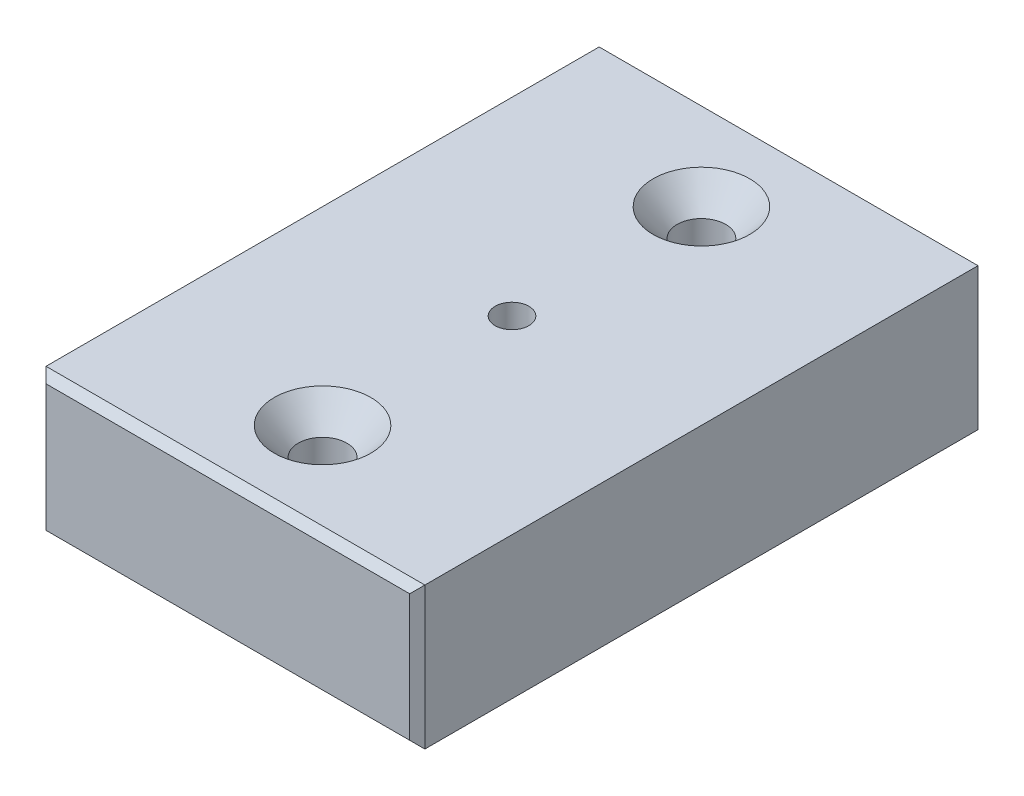
SolidWorks part; units mm, degrees
material "6061 Alloy"
ref_plane "Front Plane" through (0, 0, 0) normal (0, 0, 1) x (1, 0, 0)
ref_plane "Top Plane" through (0, 0, 0) normal (0, 1, 0) x (1, 0, 0)
ref_plane "Right Plane" through (0, 0, 0) normal (1, 0, 0) x (0, 0, -1)
sketch "Sketch1" plane through (0, 0, 0) normal (0, 0, 1) x (1, 0, 0)
  line L1 (12.7, -4.7625) -> (-12.7, -4.7625)
  line L2 (12.7, -4.7625) -> (12.7, 4.7625)
  line L3 (12.7, 4.7625) -> (-12.7, 4.7625)
  line L4 (-12.7, -4.7625) -> (-12.7, 4.7625)
  line L5 (12.7, -4.7625) -> (-12.7, 4.7625) construction
  line L6 (12.7, 4.7625) -> (-12.7, -4.7625) construction
  point P0 (0, 0)
  dimension "D1" = 9.525
  dimension "D2" = 25.4
extrude "Boss-Extrude1" add sketch "Sketch1" along normal blind 38.1
hole_wizard "CSK for #4 Flat Head Socket Cap Screw1" positions "Sketch7" profile "Sketch8" countersink size "#4" standard "ANSI Inch" end condition up to next
sketch "Sketch7" plane through (0, 4.7625, 0) normal (0, 1, 0) x (1, 0, 0)
  line L1 (12.7, 0) -> (-12.7, 0) construction
  line L3 (0, -6.35) -> (0, 0)
  line L5 (0, -6.35) -> (0, -31.75)
  line L7 (0, -38.1) -> (0, -31.75)
  line L8 (12.7, -38.1) -> (-12.7, -38.1) construction
  point P7 (0, -6.35)
  point P15 (0, -31.75)
  dimension "D1" = 6.35
sketch "Sketch8" plane through (0, 4.7625, 6.35) normal (1, 0, 0) x (0, 0, 1)
  line L0 (0, 0) -> (0, 9.525)
  line L1 (0, 9.525) -> (1.6319, 9.525)
  line L2 (1.6319, 9.525) -> (1.6319, 1.8481)
  line L3 (1.6319, 1.8481) -> (3.2385, 0)
  line L5 (3.2385, 0) -> (0, 0)
  line L6 (-1.6319, 1.8481) -> (-3.2385, 0) construction
  line L11 (0, -6.35) -> (0, 107.95) construction
  dimension "Thru Hole Dia." = 3.2639
  dimension "Thru Hole Depth" = 9.525
  dimension "Near C'Sink Dia." = 6.477
  dimension "Near C'Sink Angle" = 82
hole_wizard "#4-40 Tapped Hole1" positions "Sketch9" profile "Sketch11" tap size "#4-40" standard "ANSI Inch" end condition up to next
sketch "Sketch9" plane through (0, 4.7625, 0) normal (0, 1, 0) x (1, 0, 0)
  line L0 (12.7, 0) -> (-12.7, 0) construction
  line L1 (-12.7, -38.1) -> (-12.7, 0) construction
  point P0 (0, -19.05)
  point P7 (0, 0)
  point P10 (-12.7, -19.05)
sketch "Sketch11" plane through (0, 4.7625, 19.05) normal (1, 0, 0) x (0, 0, 1)
  line L0 (0, 0) -> (0, 9.525)
  line L1 (0, 9.525) -> (1.1303, 9.525)
  line L2 (1.1303, 9.525) -> (1.1303, 0)
  line L5 (1.1303, 0) -> (0, 0)
  line L11 (0, -6.35) -> (0, 107.95) construction
  dimension "Thru Tap Drill Dia." = 2.2606
  dimension "Thru Tap Drill Depth" = 9.525
cosmetic thread "Hole Thread1" parameters "D2"=2.8448
chamfer "Chamfer1" distance 0.508 angle 45 8 edges at (0, 4.7625, 38.1) (12.7, 0, 38.1) (0, -4.7625, 38.1) (-12.7, 0, 38.1) (0, -4.7625, 0) (12.7, 0, 0) (0, 4.7625, 0) (-12.7, 0, 0)
